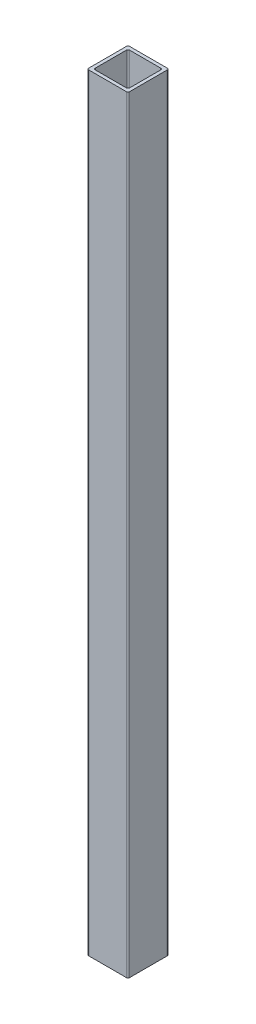
SolidWorks part; units mm, degrees
material "Hexcel AS4C (3000 Filaments)"
ref_plane "Front Plane" through (0, 0, 0) normal (0, 0, 1) x (1, 0, 0)
ref_plane "Top Plane" through (0, 0, 0) normal (0, 1, 0) x (1, 0, 0)
ref_plane "Right Plane" through (0, 0, 0) normal (1, 0, 0) x (0, 0, -1)
sketch "Sketch1" plane through (0, 0, 0) normal (0, 1, 0) x (1, 0, 0)
  line L1 (-11.5, -12.5) -> (11.5, -12.5)
  line L2 (-12.5, -11.5) -> (-12.5, 11.5)
  line L3 (-11.5, 12.5) -> (11.5, 12.5)
  line L4 (12.5, -11.5) -> (12.5, 11.5)
  line L5 (-12.5, -12.5) -> (12.5, 12.5) construction
  line L6 (-12.5, 12.5) -> (12.5, -12.5) construction
  line L7 (-9.5, -10.5) -> (9.5, -10.5)
  line L8 (-10.5, -9.5) -> (-10.5, 9.5)
  line L9 (-9.5, 10.5) -> (9.5, 10.5)
  line L10 (10.5, -9.5) -> (10.5, 9.5)
  line L11 (-10.5, -10.5) -> (10.5, 10.5) construction
  line L12 (-10.5, 10.5) -> (10.5, -10.5) construction
  arc A0 (-11.5, -12.5) -> (-12.5, -11.5) centre (-11.5, -11.5) cw
  arc A1 (11.5, 12.5) -> (12.5, 11.5) centre (11.5, 11.5) cw
  arc A2 (11.5, -12.5) -> (12.5, -11.5) centre (11.5, -11.5) ccw
  arc A3 (-12.5, 11.5) -> (-11.5, 12.5) centre (-11.5, 11.5) cw
  arc A4 (-9.5, -10.5) -> (-10.5, -9.5) centre (-9.5, -9.5) cw
  arc A5 (9.5, -10.5) -> (10.5, -9.5) centre (9.5, -9.5) ccw
  arc A6 (9.5, 10.5) -> (10.5, 9.5) centre (9.5, 9.5) cw
  arc A7 (-10.5, 9.5) -> (-9.5, 10.5) centre (-9.5, 9.5) cw
  point P0 (0, 0)
  point P18 (0, 0)
  dimension "D3" = 1
  dimension "D6" = 1
  dimension "D7" = 1
  dimension "D8" = 1
  dimension "D9" = 1
  dimension "D1" = 25
  dimension "D2" = 25
  dimension "D4" = 21
  dimension "D5" = 21
extrude "Boss-Extrude1" add sketch "Sketch1" along normal blind 470
